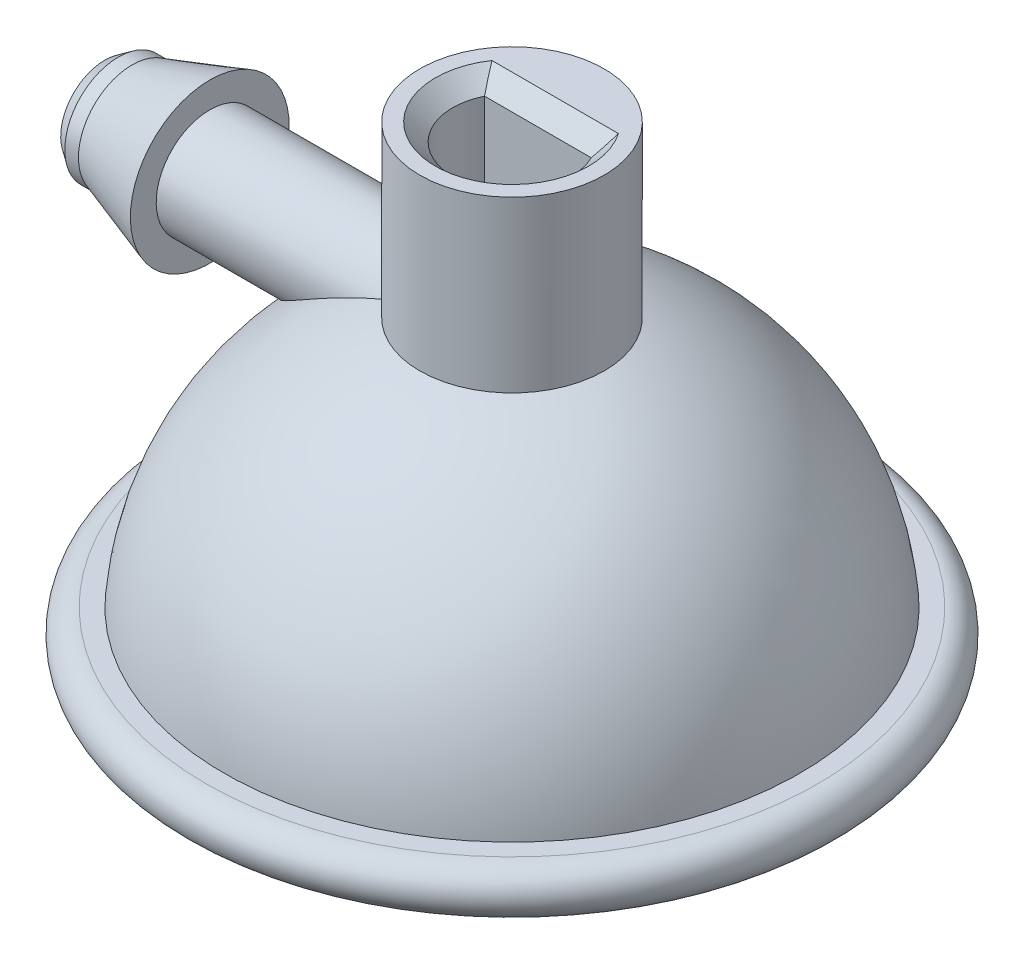
SolidWorks part; units mm, degrees
ref_plane "Front Plane" through (0, 0, 0) normal (0, 0, 1) x (1, 0, 0)
ref_plane "Top Plane" through (0, 0, 0) normal (0, 1, 0) x (1, 0, 0)
ref_plane "Right Plane" through (0, 0, 0) normal (1, 0, 0) x (0, 0, -1)
sketch "Sketch1" plane through (0, 0, 0) normal (0, 0, 1) x (1, 0, 0)
  line L0 (-2.5151, 0) -> (7.5105, 0) construction
  line L1 (2.4977, 0) -> (2.4977, 5.0158) construction
  line L3 (2.4977, 4.6362) -> (2.4977, 5.0158)
  line L5 (-2.8151, 0.4082) -> (-2.4998, 0.4072)
  line L6 (-2.5151, -0.4082) -> (-2.8151, -0.4082)
  arc A2 (-2.8151, 0.4082) -> (-2.8151, -0.4082) centre (-2.8151, 0) ccw
  arc A5 (-2.1151, 0.0013) -> (-2.5151, -0.4082) centre (-2.5234, 0) cw
  arc A6 (-2.1151, 0.0013) -> (2.4977, 4.6362) centre (2.5819, -0.0604) cw
  arc A7 (-2.4998, 0.4072) -> (2.4977, 5.0158) centre (2.4848, 0.0158) cw
revolve "Revolve1" add sketch "Sketch1" angle 360 about L1
sketch "Sketch3" plane through (0, 0, 0) normal (1, 0, 0) x (0, 0, -1)
  line L0 (-5.1915, 13.2582) -> (-5.1862, 9.6741)
  line L1 (-2.2625, 3.7845) -> (-3.8278, 3.0219)
  line L6 (-6.5841, 8.6789) -> (-6.5841, 13.2582)
  line L7 (-6.5841, 13.2582) -> (-5.1915, 13.2582)
  line L12 (-2.2625, 3.7845) -> (-5.1862, 9.6741)
  line L13 (-3.8278, 3.0219) -> (-6.5841, 8.6789)
extrude "Boss-Extrude1" [suppressed] add sketch "Sketch3" along normal blind 4.5 separate body
sketch "Sketch4" [suppressed] plane through (0, -0.0108, 5.1659) normal (0, 0.0021, -1) x (-1, 0, 0)
  line L0 (-2.997, 8.6897) -> (-2.997, 13.2897)
  line L1 (-2.997, 8.6897) -> (-1.6118, 8.6897)
  line L2 (-1.6118, 8.6897) -> (-1.6118, 13.2897)
  line L3 (-2.997, 13.2897) -> (-1.6118, 13.2897)
extrude "Cut-Extrude1" [suppressed] cut sketch "Sketch4" against normal up to next and the other way blind 4.5
sketch "Sketch5" plane through (0, 0, 0) normal (0, 0, 1) x (1, 0, 0)
  line L0 (-0.8483, 3.3998) -> (-0.8483, 3.73)
  line L1 (-4.3349, 3.3998) -> (-4.5715, 3.5649)
  line L2 (-4.0983, 3.3998) -> (-4.3349, 3.3998)
  line L3 (-4.5715, 3.5649) -> (-4.5715, 3.73)
  line L4 (-4.5715, 3.73) -> (-0.8483, 3.73)
  line L5 (-2.7483, 3.3998) -> (-0.8483, 3.3998)
  line L6 (-2.7483, 3.3998) -> (-2.7483, 2.9514)
  line L7 (-2.7483, 2.9514) -> (-4.0983, 3.3998)
  line L9 (-2.1455, 4.33) -> (-4.3035, 4.33) construction
revolve "Revolve2" add sketch "Sketch5" angle 360 about L9
sketch "Sketch7" plane through (-0.8483, 0, 0) normal (1, 0, 0) x (0, 0, -1)
  arc A2 (0.668, 3.6826) -> (-0.668, 3.6826) centre (0, 4.33) ccw construction
  circle A4 centre (0, 4.33) radius 0.9302
  circle A5 centre (0, 4.33) radius 0.6
extrude "Boss-Extrude2" add sketch "Sketch7" along normal blind 2.2
fillet "Fillet1" [suppressed] radius 0.9
ref_plane "Plane1" through (0, 5, 0) normal (0, 1, 0) x (1, 0, 0)
sketch "Sketch8" plane through (0, 5, 0) normal (0, 1, 0) x (1, 0, 0)
  line L0 (1.5404, 0.5) -> (3.455, 0.5) construction
  line L1 (1.5712, 0.45) -> (3.4242, 0.45)
  circle A0 centre (2.4977, 0) radius 1.6
  arc A1 (1.5404, 0.5) -> (3.455, 0.5) centre (2.4977, 0) ccw construction
  arc A2 (1.5712, 0.45) -> (3.4242, 0.45) centre (2.4977, 0) ccw
  dimension "D1" = 2.16
  dimension "D2" = 0.5
  dimension "D3" = 0.05
extrude "Boss-Extrude3" add sketch "Sketch8" along normal blind 2.7 and the other way blind 1
sketch "Sketch9" plane through (0, 0, 0) normal (0, 0, 1) x (1, 0, 0)
  line L0 (2.4977, 0.0202) -> (7.1105, 0.0013)
  line L2 (2.4977, 0.0202) -> (2.4977, 4.6331)
  line L3 (7.1105, 0.0013) -> (-2.1151, 0.0013) construction
  arc A0 (7.1105, 0.0013) -> (2.4977, 4.6331) centre (2.4627, -0.0146) ccw
revolve "Cut-Revolve2" cut sketch "Sketch9" angle 360 about L2
sketch "Sketch10" plane through (-4.5715, 0, 0) normal (-1, 0, 0) x (0, 0, 1)
  circle A0 centre (0, 4.33) radius 0.6
extrude "Cut-Extrude2" cut sketch "Sketch10" against normal blind 5.5
chamfer "Chamfer1" distance 0.3 angle 45 2 edges at (2.4977, 7.7, -0.45) (2.4977, 7.7, 1.03)
